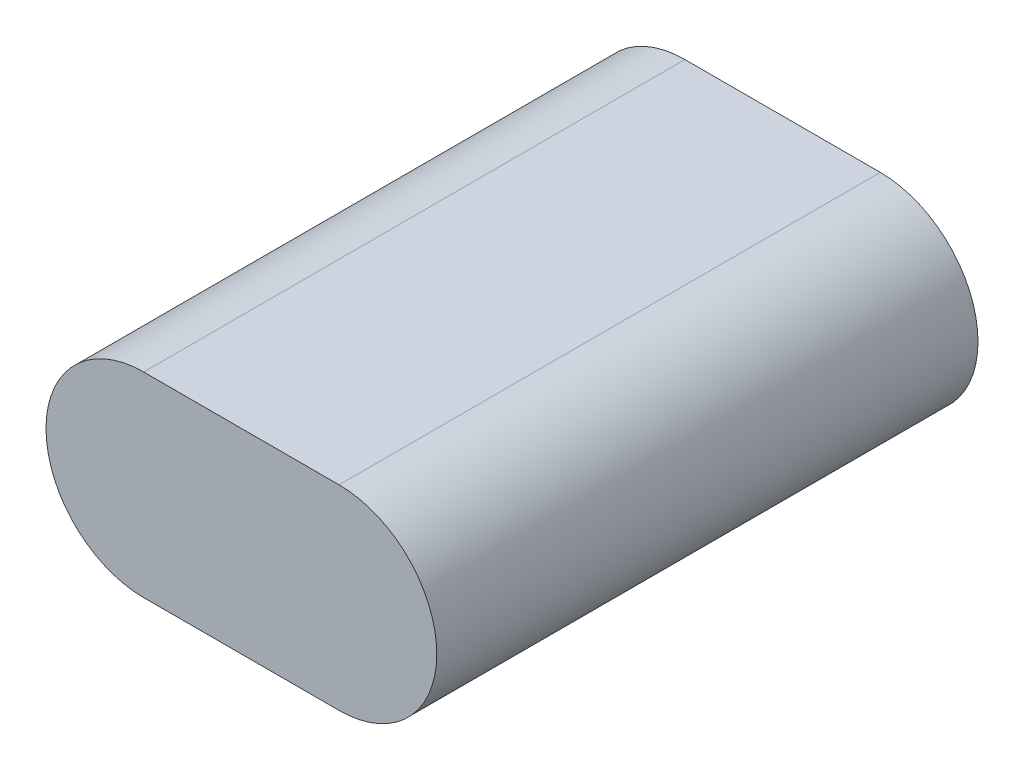
SolidWorks part; units mm, degrees
ref_plane "前视基准面" through (0, 0, 0) normal (0, 0, 1) x (1, 0, 0)
ref_plane "上视基准面" through (0, 0, 0) normal (0, 1, 0) x (1, 0, 0)
ref_plane "右视基准面" through (0, 0, 0) normal (1, 0, 0) x (0, 0, -1)
sketch "草图1" plane through (0, 0, 0) normal (0, 0, 1) x (1, 0, 0)
  line L0 (-50, 50) -> (50, 50)
  line L4 (-50, -50) -> (50, -50)
  arc A2 (-50, 50) -> (-50, -50) centre (-50, 0) ccw
  arc A3 (50, 50) -> (50, -50) centre (50, 0) cw
  point P8 (0, -50)
  point P10 (0, 50)
extrude "凸台-拉伸1" add sketch "草图1" along normal mid plane 277
